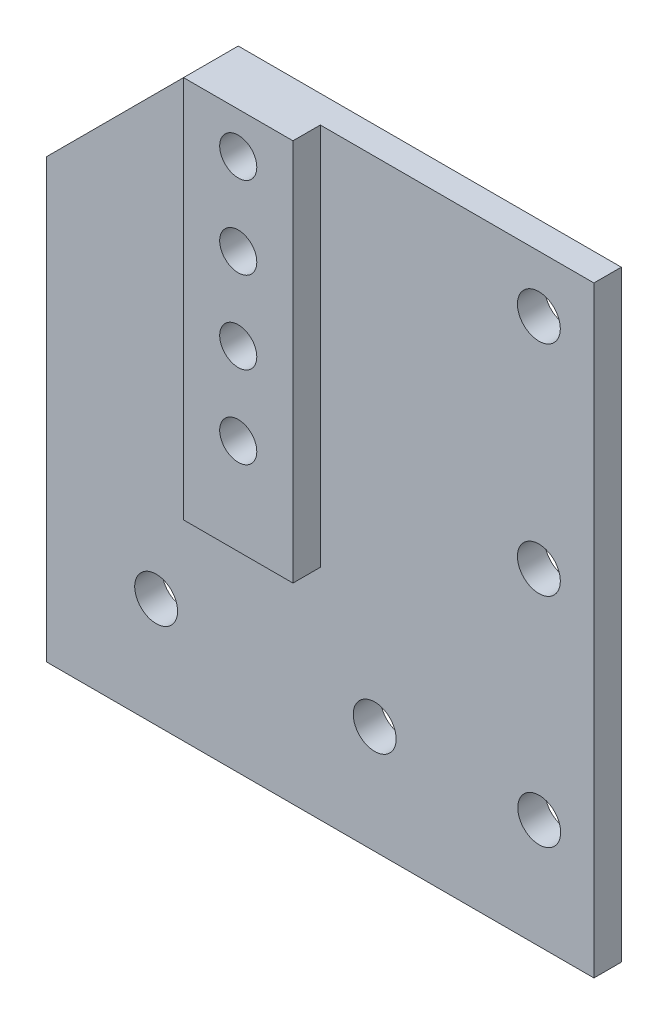
SolidWorks part; units mm, degrees
ref_plane "Front Plane" through (0, 0, 0) normal (0, 0, 1) x (1, 0, 0)
ref_plane "Top Plane" through (0, 0, 0) normal (0, 1, 0) x (1, 0, 0)
ref_plane "Right Plane" through (0, 0, 0) normal (1, 0, 0) x (0, 0, -1)
sketch "Sketch1" plane through (0, 0, 0) normal (0, 0, 1) x (1, 0, 0)
  line L15 (-266.7, -12.7) -> (-266.7, 57.15)
  line L16 (-266.7, 609.6) -> (-266.7, -16.7024) construction
  line L18 (-279.4, -12.7) -> (-266.7, -12.7)
  line L19 (-279.4, -12.7) -> (-330.2, -12.7)
  line L20 (-330.2, -12.7) -> (-330.2, 12.7)
  line L21 (-330.2, 12.7) -> (-330.2, 38.1)
  line L22 (-311.15, 57.15) -> (-330.2, 38.1)
  line L23 (-279.4, 57.15) -> (-311.15, 57.15)
  line L24 (-266.7, 57.15) -> (-279.4, 57.15)
  dimension "D1" = 69.85
  dimension "D2" = 50.8
  dimension "D3" = 12.7
extrude "Boss-Extrude1" add sketch "Sketch1" along normal blind 3.175
sketch "Sketch2" plane through (0, 0, 3.175) normal (0, 0, 1) x (1, 0, 0)
  line L0 (-787.4, 12.7) -> (-279.4, 12.7) construction
  line L1 (-787.4, -12.7) -> (-279.4, -12.7) construction
  line L10 (-273.05, 25.4) -> (-273.0882, 50.7989) construction
  line L11 (-273.05, 0) -> (-273.05, 25.4) construction
  line L12 (-273.05, -12.7) -> (-273.05, 0) construction
  line L13 (-279.4, -12.7) -> (-266.7, -12.7) construction
  line L14 (-330.2, 0) -> (-317.5, 0) construction
  line L15 (-317.5, 0) -> (-292.1, 0) construction
  line L16 (-330.2, -12.7) -> (-330.2, 12.7) construction
  dimension "D1" = 12.7
  dimension "D2" = 25.4
  dimension "D3" = 25.4
  dimension "D4" = 12.7
  dimension "D5" = 25.3989
  dimension "D6" = 12.7
  dimension "D7" = 19.05
hole_wizard "#10 Clearance Hole1" positions "Sketch3" profile "Sketch4" hole size "#10" standard "ANSI Inch" end condition through all
sketch "Sketch3" plane through (0, 0, 3.175) normal (0, 0, 1) x (1, 0, 0)
  point P30 (-273.0882, 50.5983)
  point P33 (-273.0882, 25.2365)
  point P36 (-273.05, 0)
  point P41 (-317.5, 0)
  point P44 (-292.1382, -0.1635)
sketch "Sketch4" plane through (-273.0882, 50.5983, 3.175) normal (1, 0, 0) x (0, -1, 0)
  line L0 (0, 0) -> (0, 3.175)
  line L1 (0, 3.175) -> (2.4892, 3.175)
  line L2 (2.4892, 3.175) -> (2.4892, 0)
  line L5 (2.4892, 0) -> (0, 0)
  line L11 (0, -6.35) -> (0, 107.95) construction
  dimension "Thru Hole Dia." = 4.9784
  dimension "Thru Hole Depth" = 3.175
sketch "Sketch5" plane through (0, 0, 3.175) normal (0, 0, 1) x (1, 0, 0)
  line L0 (-311.15, 12.7) -> (-298.45, 12.7)
  line L9 (-311.15, 57.15) -> (-311.15, 12.7)
  line L10 (-298.45, 12.7) -> (-298.45, 57.15)
  line L13 (-266.7, 57.15) -> (-311.15, 57.15) construction
  line L17 (-298.45, 57.15) -> (-311.15, 57.15)
  dimension "D1" = 44.45
  dimension "D2" = 12.7
extrude "Boss-Extrude2" add sketch "Sketch5" along normal blind 3.175
sketch "Sketch6" plane through (0, 0, 6.35) normal (0, 0, 1) x (1, 0, 0)
  line L0 (-304.8, 57.15) -> (-304.8, 52.3875) construction
  line L1 (-304.8, 52.3875) -> (-304.8, 42.8625) construction
  line L2 (-304.8, 42.8625) -> (-304.8, 33.3375) construction
  line L4 (-304.8, 33.3375) -> (-304.8, 23.8125) construction
  line L5 (-298.45, 57.15) -> (-311.15, 57.15) construction
  dimension "D1" = 9.525
  dimension "D2" = 4.7625
  dimension "D3" = 9.525
  dimension "D4" = 9.525
hole_wizard "#8 Clearance Hole1" positions "Sketch7" profile "Sketch8" hole size "#8" standard "ANSI Inch" end condition through all
sketch "Sketch7" plane through (0, 0, 6.35) normal (0, 0, 1) x (1, 0, 0)
  point P0 (-304.8, 42.8625)
  point P3 (-304.8, 52.3875)
  point P7 (-304.8, 33.3375)
  point P10 (-304.8, 23.8125)
sketch "Sketch8" plane through (-304.8, 42.8625, 6.35) normal (1, 0, 0) x (0, -1, 0)
  line L0 (0, 0) -> (0, 6.35)
  line L1 (0, 6.35) -> (2.1526, 6.35)
  line L2 (2.1526, 6.35) -> (2.1526, 0)
  line L5 (2.1526, 0) -> (0, 0)
  line L11 (0, -6.35) -> (0, 107.95) construction
  dimension "Thru Hole Dia." = 4.3053
  dimension "Thru Hole Depth" = 6.35
